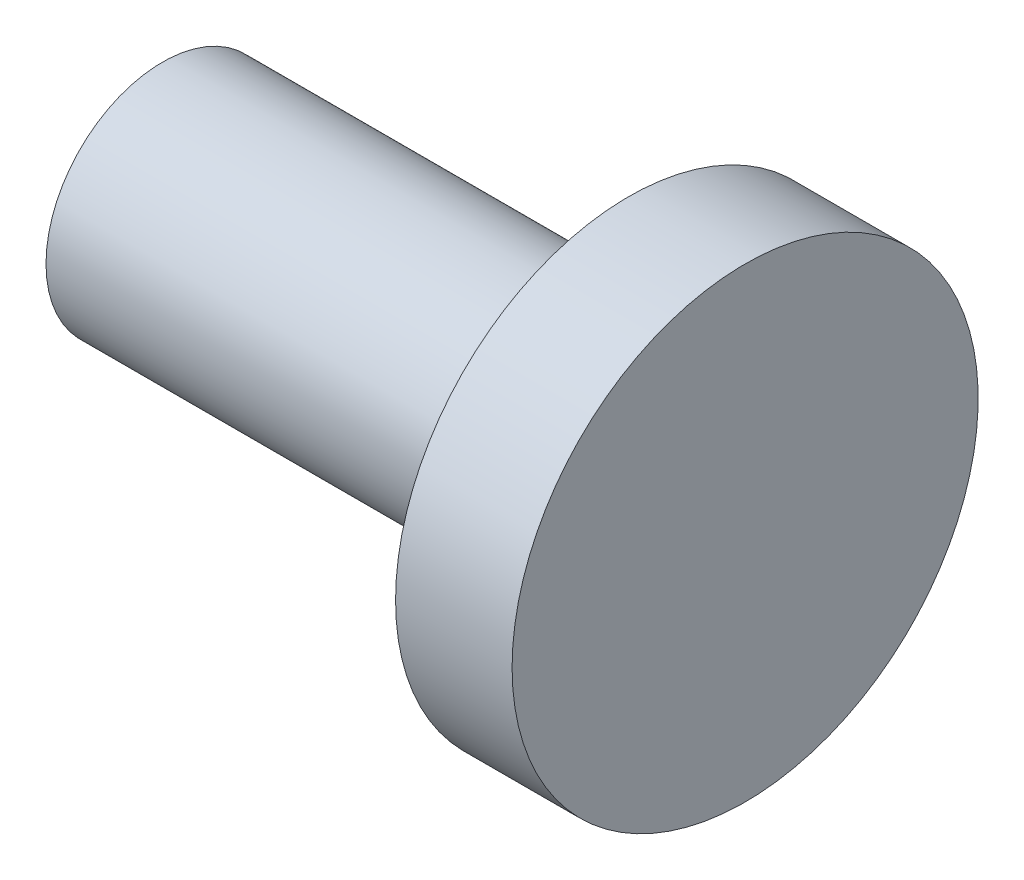
SolidWorks part; units mm, degrees
ref_plane "Ön Düzlem" through (0, 0, 0) normal (0, 0, 1) x (1, 0, 0)
ref_plane "Üst Düzlem" through (0, 0, 0) normal (0, 1, 0) x (1, 0, 0)
ref_plane "Sağ Düzlem" through (0, 0, 0) normal (1, 0, 0) x (0, 0, -1)
sketch "Çizim1" plane through (0, 0, 0) normal (0, 0, 1) x (1, 0, 0)
  line L0 (21.2982, 0) -> (21.2982, 10)
  line L1 (21.2982, 10) -> (16.2982, 10)
  line L2 (16.2982, 10) -> (16.2982, 5)
  line L3 (16.2982, 5) -> (-3.7018, 5)
  line L4 (-3.7018, 5) -> (-3.7018, 0)
  line L5 (-3.7018, 0) -> (21.2982, 0)
  dimension "D1" = 5
  dimension "D2" = 5
  dimension "D3" = 10
  dimension "D4" = 25
revolve "Döndür1" add sketch "Çizim1" angle 360 about L5
sketch "Çizim3" plane through (-3.7018, 0, 0) normal (-1, 0, 0) x (0, 0, 1)
  circle A0 centre (0, 0) radius 4
extrude "Kes-Ekstrüzyon1" cut sketch "Çizim3" against normal blind 20
thread "Diş1" pitch 1.5 method cut profile "Diş Profili1" start angle 0, offset 0, length 20, pitch 1.5, diameter 8
ref_plane "Düzlem1" through (-3.7018, 0, -4) normal (0, -1, 0) x (0, 0, -1)
sketch "Diş Profili1" plane through (-3.7018, 0, -4) normal (0, -1, 0) x (0, 0, -1)
  line L0 (0, 0) -> (0, 1.5) construction
  line L1 (0, 0) -> (0.8119, 0.4687)
  line L2 (0.8119, 0.4687) -> (0.8119, 0.6562)
  line L3 (0.8119, 0.6562) -> (0, 1.125)
  line L4 (0.8119, 0.5625) -> (0, 0.5625) construction
  line L11 (0, 0) -> (0, 1.125)
  point P2 (0, 0)
  dimension "Pitch" = 1.5
  dimension "Profile_Angle" = 60
  dimension "Profile_Land" = 0.1875
  dimension "Profile_Height" = 0.8119
